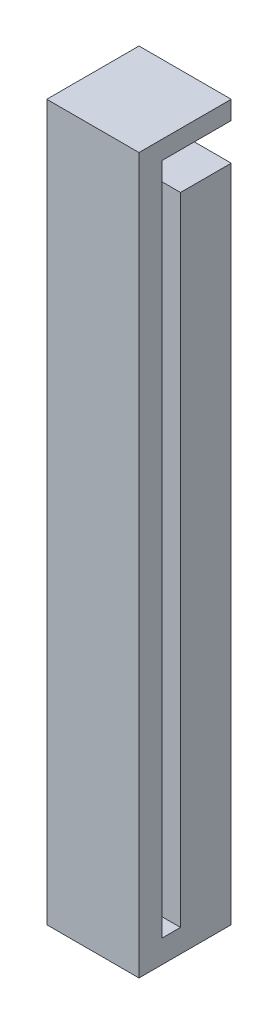
SolidWorks part; units mm, degrees
ref_plane "Front Plane" through (0, 0, 0) normal (0, 0, 1) x (1, 0, 0)
ref_plane "Top Plane" through (0, 0, 0) normal (0, 1, 0) x (1, 0, 0)
ref_plane "Right Plane" through (0, 0, 0) normal (1, 0, 0) x (0, 0, -1)
sketch "Sketch1" plane through (0, 0, 0) normal (0, 1, 0) x (1, 0, 0)
  line L1 (0, 0) -> (10, 0)
  line L2 (0, 0) -> (0, 10)
  line L3 (0, 10) -> (10, 10)
  line L4 (10, 0) -> (10, 10)
  dimension "D1" = 10
extrude "Boss-Extrude1" add sketch "Sketch1" along normal blind 75
sketch "Sketch3" plane through (0, 0, -10) normal (0, 0, -1) x (-1, 0, 0)
  line L0 (-10, 75) -> (-10, 0) construction
  line L1 (-2.5, 73) -> (-10, 73)
  line L2 (-2.5, 73) -> (-2.5, 69)
  line L3 (-2.5, 69) -> (-10, 69)
  line L4 (-10, 73) -> (-10, 69)
  line L5 (-10, 75) -> (0, 75) construction
  line L6 (0, 75) -> (0, 0) construction
  dimension "D1" = 2
  dimension "D2" = 4
  dimension "D3" = 2.5
extrude "Cut-Extrude1" cut sketch "Sketch3" against normal offset from surface (7.5 mm away) 2.5 up to face at (5, 37.5, 0)
sketch "Sketch4" plane through (0, 0, 0) normal (0, -1, 0) x (1, 0, 0)
  line L0 (2.5, -2.5) -> (2.5, -10) construction
  line L1 (2.5, -2.5) -> (2.5, -10)
  line L2 (2.5, -2.5) -> (10, -2.5) construction
  line L3 (2.5, -2.5) -> (10, -2.5)
  line L4 (10, -10) -> (0, -10) construction
  line L5 (10, -2.5) -> (2.5, -2.5)
  line L6 (10, -2.5) -> (10, -4.5)
  line L7 (10, -4.5) -> (2.5, -4.5)
  line L8 (2.5, -2.5) -> (2.5, -4.5)
  line L9 (4.5, -10) -> (2.5, -10)
  line L10 (4.5, -10) -> (4.5, -4.5)
  line L11 (4.5, -4.5) -> (2.5, -4.5)
  line L12 (2.5, -10) -> (2.5, -4.5)
  line M10 (0, -10) -> (10, -10)
  line M11 (10, -10) -> (10, 0)
  dimension "D1" = 2
  dimension "D2" = 2
extrude "Cut-Extrude2" cut sketch "Sketch4" against normal up to surface (73 mm away) contours L7 L3 L1 M11 | L10 L7 L1 M10 region at (6.25, 0, -3.5) region at (3.5, 0, -7.25) up to face at (6.25, 73, -6.25)
sketch "Sketch5" plane through (0, 0, 0) normal (0, -1, 0) x (1, 0, 0)
  line L1 (0, 0) -> (10, 0)
  line L2 (0, 0) -> (0, -10)
  line L3 (0, -10) -> (10, -10)
  line L4 (10, 0) -> (10, -10)
extrude "Boss-Extrude2" add sketch "Sketch5" along normal blind 2.5
sketch "Sketch6" plane through (0, 0, 0) normal (0, 1, 0) x (1, 0, 0)
  line L0 (10, 4.5) -> (4.5, 4.5) construction
  line L1 (2.5, 2.5) -> (6.5, 2.5)
  line L2 (2.5, 2.5) -> (2.5, 4.5)
  line L3 (2.5, 4.5) -> (6.5, 4.5)
  line L4 (6.5, 2.5) -> (6.5, 4.5)
  line L5 (4.5, 10) -> (4.5, 4.5) construction
  line L6 (2.5, 4.5) -> (4.5, 4.5)
  line L7 (2.5, 4.5) -> (2.5, 6.5)
  line L8 (2.5, 6.5) -> (4.5, 6.5)
  line L9 (4.5, 4.5) -> (4.5, 6.5)
  line L10 (3.5, 2.5) -> (3.5, 6.5) construction
  line M7 (10, 4.5) -> (4.5, 4.5)
  line M8 (4.5, 4.5) -> (4.5, 10)
  line M10 (2.5, 10) -> (2.5, 2.5)
  line M11 (2.5, 2.5) -> (10, 2.5)
  dimension "D1" = 4
extrude "Boss-Extrude3" add sketch "Sketch6" along normal up to surface (73 mm away) contours L10 L1 L4 L6 M7 | L10 L6 L8 M8 | L3 L10 L8 M10 | L10 L3 M11 M10 region at (3, 0, -3.5) region at (5, 0, -3.5) region at (3, 0, -5.5) region at (4, 0, -5.5) up to face at (6.25, 73, -6.25)
sketch "Sketch7" plane through (0, -2.5, 0) normal (0, -1, 0) x (1, 0, 0)
  line L0 (5, 0) -> (5, -10) construction
  line L1 (10, 0) -> (0, 0) construction
  line L2 (0, -10) -> (10, -10) construction
  circle A0 centre (5, -5) radius 2
  dimension "D1" = 4
extrude "Cut-Extrude3" cut sketch "Sketch7" against normal blind 2
